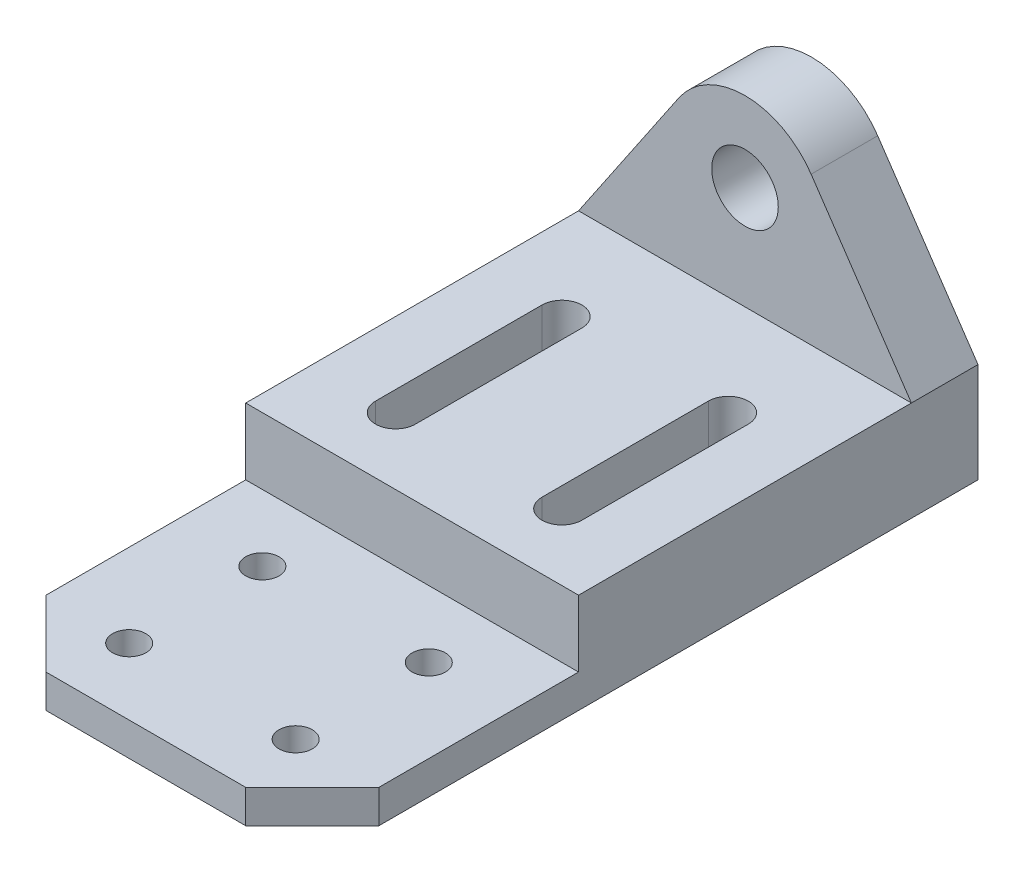
SolidWorks part; units mm, degrees
ref_plane "Front Plane" through (0, 0, 0) normal (0, 0, 1) x (1, 0, 0)
ref_plane "Top Plane" through (0, 0, 0) normal (0, 1, 0) x (1, 0, 0)
ref_plane "Right Plane" through (0, 0, 0) normal (1, 0, 0) x (0, 0, -1)
sketch "Sketch1" plane through (0, 0, 0) normal (1, 0, 0) x (0, 0, -1)
  line L0 (-100, 0) -> (100, 0)
  line L1 (100, 0) -> (100, 85)
  line L2 (100, 85) -> (80, 85)
  line L3 (80, 85) -> (80, 30)
  line L4 (80, 30) -> (-20, 30)
  line L5 (-20, 30) -> (-20, 10)
  line L6 (-20, 10) -> (-100, 10)
  line L7 (-100, 10) -> (-100, 0)
  line L8 (0, 0) -> (0, 128.7823) construction
  point P3 (-20, 20)
  dimension "D1" = 200
  dimension "D2" = 85
  dimension "D3" = 20
  dimension "D4" = 80
  dimension "D5" = 30
  dimension "D6" = 10
  dimension "D7" = 80
extrude "Boss-Extrude1" add sketch "Sketch1" along normal blind 50 and the other way blind 50
chamfer "Chamfer1" distance 20 distance2 20 2 edges at (-50, 5, 100) (50, 5, 100)
hole_wizard "Hole1" positions "Sketch2" profile "Sketch3" legacy end condition through all
sketch "Sketch2" plane through (0, 10, 0) normal (0, 1, 0) x (1, 0, 0)
  line L0 (-50, -20) -> (-50, -80) construction
  line L1 (-30, -100) -> (30, -100) construction
  point P0 (-25, -40)
  point P2 (-25, -80)
  point P9 (-15.023, -41.2642)
  point P10 (-25, -40)
  dimension "D1" = 40
  dimension "D2" = 25
  dimension "D3" = 20
sketch "Sketch3" plane through (-25, 10, 40) normal (1, 0, 0) x (0, 0, 1)
  line L0 (0, 0) -> (0, 10)
  line L1 (0, 10) -> (5, 10)
  line L2 (5, 10) -> (5, 0)
  line L3 (5, 0) -> (0, 0)
  line L4 (0, 110) -> (0, -10) construction
  dimension "Diameter" = 10
  dimension "Depth" = 10
mirror "Mirror1" about plane through (0, 0, 0) normal (1, 0, 0) of "Hole1"
sketch "Sketch4" plane through (0, 30, 0) normal (0, 1, 0) x (1, 0, 0)
  line L0 (-25, 50) -> (-25, 0) construction
  line L1 (-19, 50) -> (-19, 0)
  line L2 (-31, 50) -> (-31, 0)
  line L4 (-50, 100) -> (50, 100) construction
  line L5 (-50, 80) -> (-50, -20) construction
  line L6 (0, -46.75) -> (0, 46.75) construction
  line L7 (25, 50) -> (25, 0) construction
  line L8 (19, 50) -> (19, 0)
  line L9 (31, 50) -> (31, 0)
  arc A0 (-19, 50) -> (-31, 50) centre (-25, 50) ccw
  arc A1 (-31, 0) -> (-19, 0) centre (-25, 0) ccw
  arc A2 (19, 50) -> (31, 50) centre (25, 50) cw
  arc A3 (31, 0) -> (19, 0) centre (25, 0) cw
  point P2 (-25, 25)
  point P15 (25, 25)
  dimension "D1" = 50
  dimension "D2" = 50
  dimension "D3" = 25
  dimension "D4" = 12
extrude "Cut-Extrude1" cut sketch "Sketch4" against normal through all
sketch "Sketch7" plane through (0, 0, -80) normal (0, 0, 1) x (1, 0, 0)
  line L1 (-50, 85) -> (50, 85)
  line L2 (-50, 85) -> (-50, 30)
  line L3 (-50, 30) -> (50, 30)
  line L4 (50, 85) -> (50, 30)
extrude "Cut-Extrude2" cut sketch "Sketch7" against normal through all
sketch "Sketch8" plane through (0, 0, -100) normal (0, 0, -1) x (-1, 0, 0)
  line L0 (50, 30) -> (-50, 30) construction
  line L1 (50, 30) -> (-50, 30)
  line L2 (50, 0) -> (-50, 0) construction
  line L3 (-50, 30) -> (-19.8676, 74.4639)
  line L4 (50, 30) -> (19.8676, 74.4639)
  arc A0 (19.8676, 74.4639) -> (-19.8676, 74.4639) centre (0, 61) ccw
  dimension "D1" = 48
  dimension "D2" = 61
extrude "Boss-Extrude2" add sketch "Sketch8" against normal blind 20
hole_wizard "Hole2" positions "Sketch9" profile "Sketch10" legacy end condition through all
sketch "Sketch9" plane through (0, 0, -80) normal (0, 0, 1) x (1, 0, 0)
  point P0 (0, 61)
sketch "Sketch10" plane through (0, 61, -80) normal (1, 0, 0) x (0, -1, 0)
  line L0 (0, 0) -> (0, 20)
  line L1 (0, 20) -> (10, 20)
  line L2 (10, 20) -> (10, 0)
  line L3 (10, 0) -> (0, 0)
  line L4 (0, 110) -> (0, -10) construction
  dimension "Diameter" = 20
  dimension "Depth" = 20
